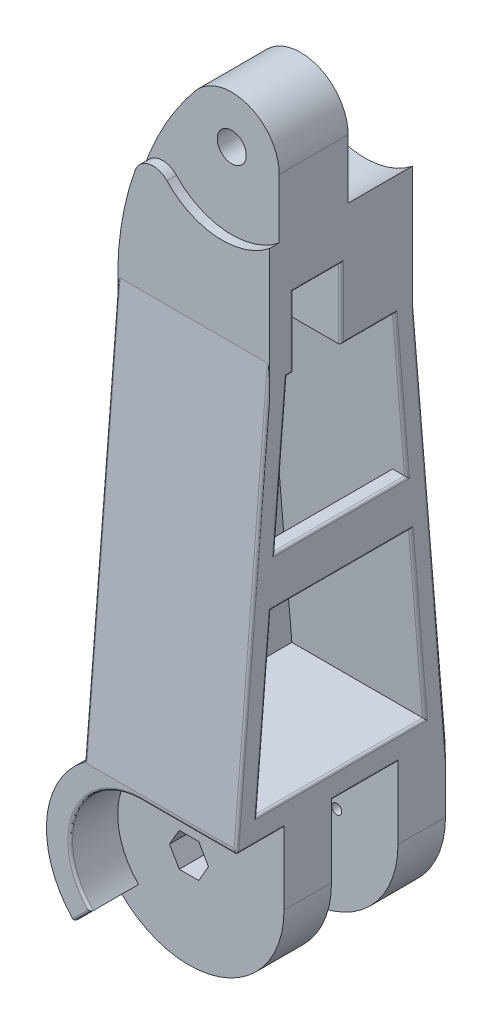
SolidWorks part; units mm, degrees
note: '?' marks a value the reader was unsure of.
ref_plane "前视基准面" through (0, 0, 0) normal (0, 0, 1) x (1, 0, 0)
ref_plane "上视基准面" through (0, 0, 0) normal (0, 1, 0) x (1, 0, 0)
ref_plane "右视基准面" through (0, 0, 0) normal (1, 0, 0) x (0, 0, -1)
other "Configuration Table"
sketch "草图1" plane through (0, 0, 0) normal (0, 0, 1) x (1, 0, 0)
  line L1 (0, 0) -> (0, 134.6291)
  line L2 (-32, 16) -> (-32, 101)
  line L3 (-10, 134.6291) -> (-20, 0) construction
  arc A0 (-17.741, 140.9597) -> (0, 134.6291) centre (-10, 134.6291) cw
  arc A1 (-32, 16) -> (0, 0) centre (-20, 0) ccw
  arc A2 (-17.741, 140.9597) -> (-32, 101) centre (31.1216, 101) ccw
  dimension "D2" = 10
  dimension "D4" = 20
  dimension "D1" = 135
  dimension "D3" = 32
  dimension "D6" = 85
extrude "凸台-拉伸1" add sketch "草图1" along normal mid plane 44
ref_axis "底部旋转基准轴" through (-20, 0, 0) along (0, 0, 1)?
ref_axis "顶部旋转基准轴" through (-10, 134.6291, 0) along (0, 0, 1)?
ref_plane "旋转基准面" through (-19.8903, 1.4774, 0) normal (0.9973, -0.0741, 0) x (0, 0, -1)
ref_plane "主基准面" through (0, 0, 0) normal (0, 1, 0) x (0, 0, 1)
sketch "草图4" plane through (9.5905, 7.0285, 0) normal (0, 0, 1) x (-0.3879, 0.9217, 0)
  line L0 (18.8255, 24.1815) -> (11.0675, 5.7475)
  line L2 (-2.758, 11.566) -> (121.3297, -40.6569) construction
  line L3 (-0.6618, 43.8904) -> (-2.5491, 48.5206)
  line L4 (-2.758, 11.566) -> (11.0675, 5.7475)
  arc A1 (18.8255, 24.1815) -> (-0.6618, 43.8904) centre (5, 30) ccw
  arc A3 (24.402, 34.854) -> (-2.758, 11.566) centre (5, 30) ccw construction
  arc A4 (24.402, 34.854) -> (-2.758, 11.566) centre (5, 30) ccw
  dimension "D1" = 15
  dimension "D2" = 45
extrude "切除-拉伸2" cut sketch "草图4" against normal blind 12 and the other way blind 2 contours L3 A4 L4 L0 A1
sketch "草图17" plane through (0, 0, -12) normal (0, 0, 1) x (1, 0, 0)
  circle A0 centre (-20, 0) radius 4
  circle A1 centre (-20, 0) radius 2.5
  dimension "D1" = 5
  dimension "D2" = 8
extrude "锁紧轴承-凸台-拉伸" add sketch "草图17" along normal blind 1
sketch "草图9" plane through (0, 0, 22) normal (0, 0, 1) x (1, 0, 0)
  line L0 (0, 0) -> (0, 15) construction
  line L2 (-30.6066, -10.6066) -> (-34.1421, -14.1421) construction
  line L3 (-20, 15) -> (0, 15) construction
  line L4 (0, 0) -> (0, 15)
  line L5 (-30.6066, -10.6066) -> (-34.1421, -14.1421)
  line L6 (-20, 15) -> (0, 15)
  arc A1 (-34.1421, -14.1421) -> (0, 0) centre (-20, 0) ccw construction
  arc A2 (-20, 15) -> (-30.6066, -10.6066) centre (-20, 0) ccw construction
  arc A3 (-34.1421, -14.1421) -> (0, 0) centre (-20, 0) ccw
  arc A4 (-20, 15) -> (-30.6066, -10.6066) centre (-20, 0) ccw
extrude "切除-拉伸4" cut sketch "草图9" against normal blind 10
sketch "草图10" plane through (0, 0, 0) normal (0, 1, 0) x (0, 0, 1)
  line L0 (-40.4435, -20) -> (48.0265, -20) construction
  line L1 (0, -20) -> (61.499, -20) construction
  line L2 (-22, -9.5) -> (-19, -9.5)
  line L3 (-22, 0) -> (-22, -40) construction
  line L4 (-19, -9.5) -> (-19, -15.5)
  line L5 (-19, -15.5) -> (-15, -15.5)
  line L6 (-15, -15.5) -> (-15, -17.45)
  line L8 (12, -34.1421) -> (12, 0) construction
  line L9 (12, -17.45) -> (12, -20)
  line L10 (12, -20) -> (-22, -20)
  line L11 (-22, -20) -> (-22, -9.5)
  line L12 (-12, -34.1421) -> (-12, 0) construction
  line L13 (12, -17.45) -> (-15, -17.45)
  dimension "D1" = 21
  dimension "D2" = 9
  dimension "D3" = 3
  dimension "D4" = 5.1
  dimension "D5" = 3
revolve "切除-旋转1" cut sketch "草图10" angle 360 about L0
sketch "草图11" plane through (0, 0, 12) normal (0, 0, 1) x (1, 0, 0)
  line L1 (-15.9008, 0) -> (-17.9504, 3.55)
  line L2 (-17.9504, 3.55) -> (-22.0496, 3.55)
  line L3 (-22.0496, 3.55) -> (-24.0992, 0)
  line L4 (-24.0992, 0) -> (-22.0496, -3.55)
  line L5 (-22.0496, -3.55) -> (-17.9504, -3.55)
  line L6 (-17.9504, -3.55) -> (-15.9008, 0)
  circle A0 centre (-20, 0) radius 3.55 construction
  dimension "D1" = 7.1
extrude "切除-拉伸5" cut sketch "草图11" against normal blind 6
sketch "草图12" plane through (0, 0, 0) normal (1, 0, 0) x (0, 0, -1)
  line L0 (-22, 16) -> (-15, 101)
  line L1 (-22, 101) -> (22, 101) construction
  line L2 (-15, 101) -> (-15, 144.6291)
  line L3 (22, 144.6291) -> (-22, 144.6291) construction
  line L4 (-15, 144.6291) -> (-22, 144.6291)
  line L5 (-22, 144.6291) -> (-22, 16)
  line L6 (0, 140.9597) -> (0, 101) construction
  dimension "D1" = 15
extrude "切除-拉伸6" cut sketch "草图12" against normal through all
mirror "镜向1" about plane through (0, 0, 0) normal (0, 0, 1) of "切除-拉伸6"
sketch "草图13" plane through (0, 0, -15) normal (0, 0, 1) x (1, 0, 0)
  circle A0 centre (-10, 134.6291) radius 16
  circle A1 centre (-24.5484, 120.9052) radius 4
  arc A2 (-17.741, 140.9597) -> (-32, 101) centre (31.1216, 101) ccw construction
  arc A3 (-17.741, 140.9597) -> (-32, 101) centre (31.1216, 101) ccw
  arc M2 (-17.741, 140.9597) -> (0, 134.6291) centre (-10, 134.6291) cw
  line M3 (0, 134.6291) -> (0, 101)
  arc M5 (-32, 101) -> (-17.741, 140.9597) centre (31.1216, 101) cw
  dimension "D1" = 32
  dimension "D2" = 8
extrude "切除-拉伸7" cut sketch "草图13" along normal blind 13.5 contours A0 M3 M2 M5 | A0 M5 M2 M3 | A0 A1 M5
sketch "草图14" plane through (0, 0, 15) normal (0, 0, 1) x (1, 0, 0)
  circle A0 centre (-10, 134.6291) radius 16
  arc A1 (-21.6387, 123.65) -> (0, 122.1391) centre (-10, 134.6291) ccw construction
  circle A2 centre (-24.5484, 120.9052) radius 4
  arc A3 (-17.741, 140.9597) -> (-32, 101) centre (31.1216, 101) ccw construction
  arc A4 (-17.741, 140.9597) -> (-32, 101) centre (31.1216, 101) ccw
  arc M2 (0, 134.6291) -> (-17.741, 140.9597) centre (-10, 134.6291) ccw
  arc M3 (-17.741, 140.9597) -> (-32, 101) centre (31.1216, 101) ccw
  line M5 (0, 101) -> (0, 134.6291)
  dimension "D1" = 8
extrude "切除-拉伸8" cut sketch "草图14" against normal blind 2 contours A0 M5 M3 M2 | A0 M3 M5 M2 | A2 A0 M3
sketch "草图15" plane through (0, 0, -1.5) normal (0, 0, -1) x (-1, 0, 0)
  circle A0 centre (10, 134.6291) radius 3.05
  dimension "D1" = 6.1
extrude "切除-拉伸9" cut sketch "草图15" against normal through all
sketch "草图16" plane through (0, 0, 0) normal (-1, 0, 0) x (0, 0, 1)
  line L1 (11.3159, 97) -> (17.657, 20)
  line L2 (17.657, 20) -> (-17.657, 20)
  line L3 (-17.657, 20) -> (-11.3159, 97)
  line L5 (22, 16) -> (15, 101) construction
  line L6 (-22, 16) -> (-15, 101) construction
  line L7 (22, 16) -> (-22, 16) construction
  line L8 (-11.3159, 97) -> (11.3159, 97)
  line L14 (15, 101) -> (-15, 101) construction
  dimension "D1" = 4
  dimension "D2" = 4
  dimension "D3" = 4
  dimension "D4" = 4
extrude "切除-拉伸11" cut sketch "草图16" along normal offset from surface (28 mm away) 4 up to face at (-32, 58.5, 0)
sketch "草图20" plane through (0, 0, 0) normal (0, 0, 1) x (1, 0, 0)
  line L0 (0, 0) -> (0, 134.6291) construction
  line L1 (-3, 66) -> (0, 66)
  line L2 (-3, 66) -> (-3, 56)
  line L3 (-3, 56) -> (0, 56)
  line L4 (0, 66) -> (0, 56)
  line L5 (-32, 16) -> (0, 16) construction
  dimension "D1" = 3
  dimension "D2" = 10
  dimension "D3" = 40
extrude "凸台-拉伸4" add sketch "草图20" along normal up to next and the other way up to next
sketch "草图18" plane through (0, 0, 2) normal (0, 0, -1) x (-1, 0, 0)
  circle A0 centre (20, 0) radius 2.5
  circle A1 centre (20, 0) radius 4
  circle M2 centre (20, 0) radius 2.55
  dimension "D1" = 5
  dimension "D2" = 8
extrude "凸台-拉伸3" add sketch "草图18" along normal blind 1 contours A1 M2
sketch "草图19" plane through (0, 0, -19) normal (0, 0, -1) x (-1, 0, 0)
  line L0 (20, 0) -> (20, 12.2947) construction
  circle A0 centre (12.9, 0) radius 1.05
  circle A1 centre (27.1, 0) radius 1.05
  dimension "D1" = 2.1
  dimension "D2" = 7.1
extrude "切除-拉伸12" cut sketch "草图19" against normal up to next
sketch "草图21" plane through (-28, 0, 0) normal (1, 0, 0) x (0, 0, -1)
  line L0 (-17.657, 20) -> (17.657, 20) construction
  line L1 (-5, 20) -> (5, 20)
  line L2 (-5, 20) -> (-5, 25)
  line L3 (-5, 25) -> (5, 25)
  line L4 (5, 20) -> (5, 25)
  line L5 (0, 134.6291) -> (0, 0) construction
  point P6 (0, 20)
  dimension "D1" = 5
  dimension "D2" = 10
extrude "走延长线-切除-拉伸1" cut sketch "草图21" against normal up to next
sketch "草图22" plane through (0, 0, 0) normal (0, 0, 1) x (1, 0, 0)
  line L0 (0, 112) -> (-28, 97)
  line L1 (0, 0) -> (0, 134.6291) construction
  line L2 (-28, 97) -> (0, 97)
  line L3 (0, 97) -> (0, 112)
  line L4 (-28, 97) -> (0, 97) construction
  point P4 (0, 101)
  point P6 (0, 95.5178)
  point P8 (0, 0)
  point P12 (-24.4793, 97)
  dimension "D2" = 15
extrude "走延长线-切除-拉伸2" cut sketch "草图22" along normal blind 10
fillet "圆角2" radius 0.5 27 edges at (-32, 58.5, -18.5) (-32, 58.5, 18.5) (0, 58.5, 18.5) (0, 58.5, -18.5) (0, 20, 0) (0, 38, -16.1747) (0, 81.5, -12.5923) (0, 97, -5.6579) (0, 97, 10.6579) (0, 38, 16.1747) (0, 81.5, 12.5923) (-10, 15, 22) (-34.1421, -14.1421, -5) (-32.3744, -12.3744, 22) (-34.1421, -14.1421, 17) (-33.8582, 5.7403, 22) (0, 15, 17) (0, 15, -5) (0, 56, 0) (0, 66, 0) (-32, 25, 0) (-32, 22.5, -5) (-32, 20, 0) (-32, 22.5, 5) (0, 104.5, 10) (0, 112, 5) (0, 104.5, 0)
